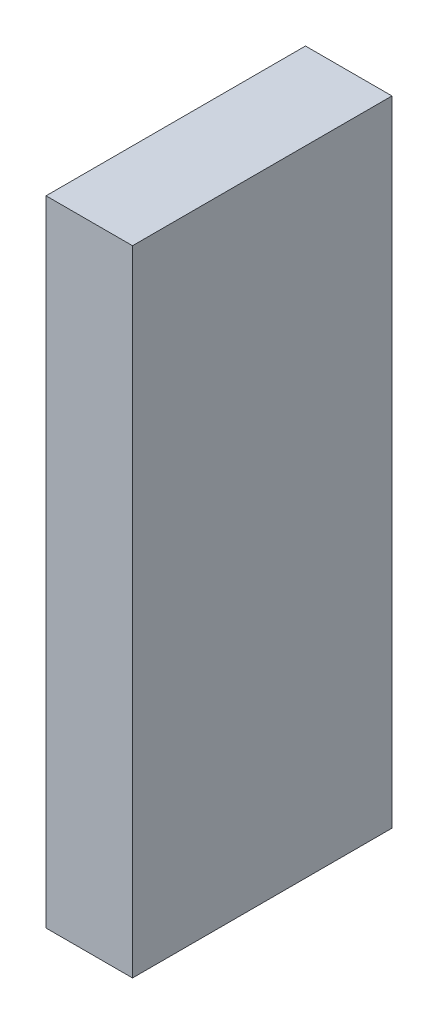
SolidWorks part; units mm, degrees
ref_plane "Front Plane" through (0, 0, 0) normal (0, 0, 1) x (1, 0, 0)
ref_plane "Top Plane" through (0, 0, 0) normal (0, 1, 0) x (1, 0, 0)
ref_plane "Right Plane" through (0, 0, 0) normal (1, 0, 0) x (0, 0, -1)
sketch "Sketch1" plane through (0, 0, 0) normal (0, 1, 0) x (1, 0, 0)
  line L1 (-15, 45) -> (15, 45)
  line L2 (-15, 45) -> (-15, -45)
  line L3 (-15, -45) -> (15, -45)
  line L4 (15, 45) -> (15, -45)
  line L5 (-15, 45) -> (15, -45) construction
  line L6 (-15, -45) -> (15, 45) construction
  point P0 (0, 0)
  dimension "D1" = 30
  dimension "D2" = 90
extrude "Boss-Extrude1" add sketch "Sketch1" along normal mid plane 220
